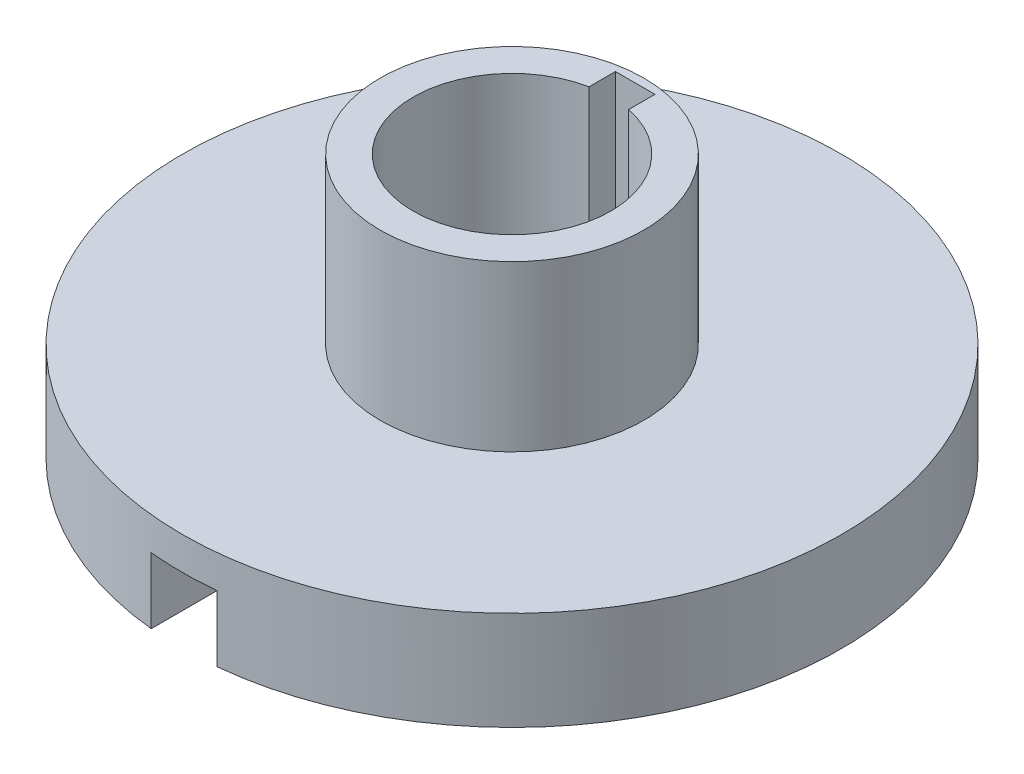
SolidWorks part; units mm, degrees
ref_plane "Front Plane" through (0, 0, 0) normal (0, 0, 1) x (1, 0, 0)
ref_plane "Top Plane" through (0, 0, 0) normal (0, 1, 0) x (1, 0, 0)
ref_plane "Right Plane" through (0, 0, 0) normal (1, 0, 0) x (0, 0, -1)
sketch "Sketch1" plane through (0, 0, 0) normal (0, 1, 0) x (1, 0, 0)
  line L0 (-3, 14.6969) -> (-3, 18.6969)
  line L1 (-3, 18.6969) -> (3, 18.6969)
  line L2 (3, 18.6969) -> (3, 14.6969)
  circle A0 centre (0, 0) radius 50
  arc A1 (-3, 14.6969) -> (3, 14.6969) centre (0, 0) ccw
  circle A2 centre (0, 0) radius 20
  dimension "D1" = 100
  dimension "D2" = 30
  dimension "D3" = 40
  dimension "D4" = 6
  dimension "D5" = 4
  dimension "D6" = 4
extrude "Boss-Extrude1" add sketch "Sketch1" along normal blind 15 contours A0 A2 region at (-48.5858, 0, 0)
extrude "Boss-Extrude2" add sketch "Sketch1<3>" along normal blind 40 contours A2 A1 L0 L1 L2 region at (-19.4343, 0, 0)
sketch "Sketch1<3>" plane through (0, 0, 0) normal (0, 1, 0) x (1, 0, 0) same geometry as "Sketch1"
sketch "Sketch2" plane through (0, 0, 0) normal (0, -1, 0) x (1, 0, 0)
  line L0 (-5, 49.7494) -> (-5, -49.7494)
  line L2 (5, 49.7494) -> (5, -49.7494)
  circle A3 centre (0, 0) radius 50 construction
  arc A4 (-5, -49.7494) -> (5, -49.7494) centre (0, 0) ccw
  arc A5 (5, 49.7494) -> (-5, 49.7494) centre (0, 0) ccw
  dimension "D1" = 10
  dimension "D2" = 5
extrude "Cut-Extrude1" cut sketch "Sketch2" against normal blind 10
